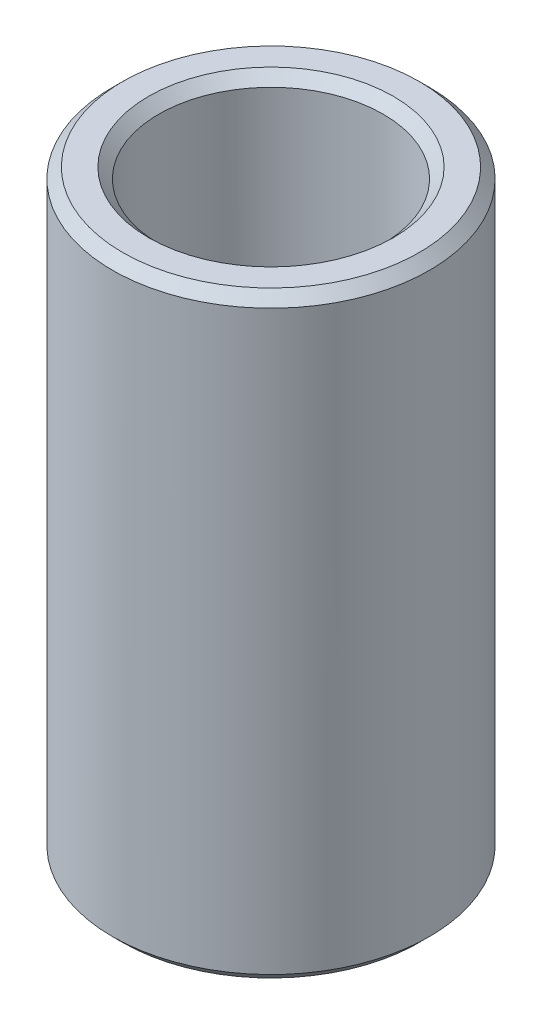
SolidWorks part; units mm, degrees
ref_plane "Front Plane" through (0, 0, 0) normal (0, 0, 1) x (1, 0, 0)
ref_plane "Top Plane" through (0, 0, 0) normal (0, 1, 0) x (1, 0, 0)
ref_plane "Right Plane" through (0, 0, 0) normal (1, 0, 0) x (0, 0, -1)
sketch "Sketch1" plane through (0, 0, 0) normal (0, 1, 0) x (1, 0, 0)
  circle A0 centre (0, 0) radius 32.5
  dimension "SLEEVE_OD" = 65
extrude "Boss-Extrude1" add sketch "Sketch1" along normal blind 122.5423
sketch "Sketch2" plane through (0, 0, 0) normal (0, 1, 0) x (1, 0, 0)
  circle A0 centre (0, 0) radius 23.0006
  dimension "BORE_D" = 46.0012
extrude "Cut-Extrude1" cut sketch "Sketch2" along normal through all
chamfer "Chamfer1" distance 2.1042 angle 45 4 edges at (0, 122.5423, 23.0006) (0, 0, 23.0006) (0, 0, 32.5) (0, 122.5423, 32.5)
